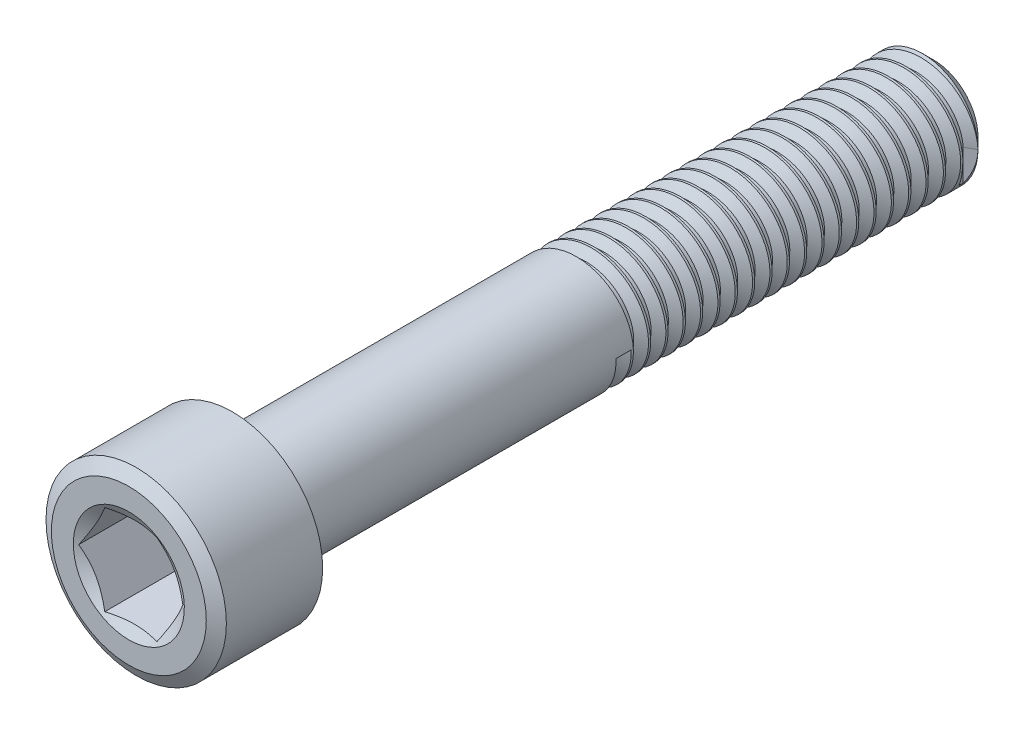
SolidWorks part; units mm, degrees
material "Stainless Steel (ferritic)"
ref_plane "Front Plane" through (0, 0, 0) normal (0, 0, 1) x (1, 0, 0)
ref_plane "Top Plane" through (0, 0, 0) normal (0, 1, 0) x (1, 0, 0)
ref_plane "Right Plane" through (0, 0, 0) normal (1, 0, 0) x (0, 0, -1)
sketch "Sketch1" plane through (0, 0, 0) normal (1, 0, 0) x (0, 0, -1)
  line L0 (0, 0) -> (66.2642, 0) construction
  line L1 (0, 0) -> (0, 5.582)
  line L2 (0, 5.582) -> (0.53, 6.5)
  line L3 (0.53, 6.5) -> (7.47, 6.5)
  line L4 (7.47, 6.5) -> (8, 5.582)
  line L5 (8, 5.582) -> (8, 4)
  line L6 (8, 4) -> (58, 4)
  line L7 (58, 4) -> (58, 0)
  line L8 (58, 0) -> (0, 0)
  dimension "D1" = 4
  dimension "D2" = 50
  dimension "D3" = 8
  dimension "D4" = 6.5
  dimension "D5" = 30
  dimension "D6" = 30
  dimension "D7" = 0.53
  dimension "D8" = 0.53
revolve "Revolve1" add sketch "Sketch1" angle 360 about L0
chamfer "Chamfer1" distance 0.8 angle 45 1 edges at (4, 0, -58)
sketch "Sketch2" plane through (0, 0, 0) normal (0, 0, 1) x (1, 0, 0)
  line L1 (-1.8764, -3.25) -> (1.8764, -3.25)
  line L2 (1.8764, -3.25) -> (3.7528, 0)
  line L3 (3.7528, 0) -> (1.8764, 3.25)
  line L4 (1.8764, 3.25) -> (-1.8764, 3.25)
  line L5 (-1.8764, 3.25) -> (-3.7528, 0)
  line L6 (-3.7528, 0) -> (-1.8764, -3.25)
  circle A0 centre (0, 0) radius 3.25 construction
  dimension "D1" = 6.5
extrude "Cut-Extrude1" cut sketch "Sketch2" against normal blind 6
sketch "Sketch3" plane through (0, 0, 0) normal (1, 0, 0) x (0, 0, -1)
  line L0 (0, 0) -> (40.9537, 0) construction
  line L1 (0, 0) -> (0, 4)
  line L2 (0, 5.582) -> (0, -5.582) construction
  line L3 (0, 4) -> (2.3094, 0)
  line L4 (2.3094, 0) -> (0, 0)
  line L5 (6, 3.25) -> (6, 0)
  line L6 (6, 0) -> (7.8764, 0)
  line L7 (7.8764, 0) -> (6, 3.25)
  dimension "D1" = 30
  dimension "D2" = 30
  dimension "D3" = 4
revolve "Cut-Revolve1" cut sketch "Sketch3" angle 360 about L0
thread "Thread1" pitch 1.25 method cut profile "Thread Profile2" start angle 0, offset 0, length 25, pitch 1.25, diameter 8
ref_plane "Plane2" through (4, 0, -57.2) normal (0, -1, 0) x (1, 0, 0)
sketch "Thread Profile2" plane through (4, 0, -57.2) normal (0, -1, 0) x (1, 0, 0)
  line L0 (0, 0) -> (0, 1.25) construction
  line L11 (0, 0) -> (0, 1.0937)
  line L12 (0, 1.0937) -> (-0.6766, 0.7031)
  line L13 (-0.6766, 0.7031) -> (-0.6766, 0.3906)
  line L15 (-0.6766, 0.3906) -> (0, 0)
  line L17 (-0.6766, 0.5469) -> (0, 0.5469) construction
  point P2 (0, 0)
  dimension "Pitch" = 1.25
  dimension "Profile_Angle" = 60
  dimension "Profile_Land" = 0.3125
  dimension "Profile_Height" = 0.6766
sketch "Sketch20" plane through (0, 0, 0) normal (0, 1, 0) x (1, 0, 0)
  line L4 (4, 57.2) -> (3.3234, 56.8094)
  line L5 (3.3234, 56.8094) -> (3.3234, 56.4969)
  line L6 (3.3234, 56.4969) -> (4, 56.1063)
  line L7 (4, 56.1063) -> (4, 57.2)
  line L8 (4, 57.2) -> (3.3234, 56.8094)
  line L9 (3.3234, 56.8094) -> (3.3234, 56.4969)
  line L10 (3.3234, 56.4969) -> (4, 56.1063)
  line L11 (4, 56.1063) -> (4, 57.2)
  dimension "D1" = 0
extrude "Cut-Extrude2" cut sketch "Sketch20" against normal blind 10
